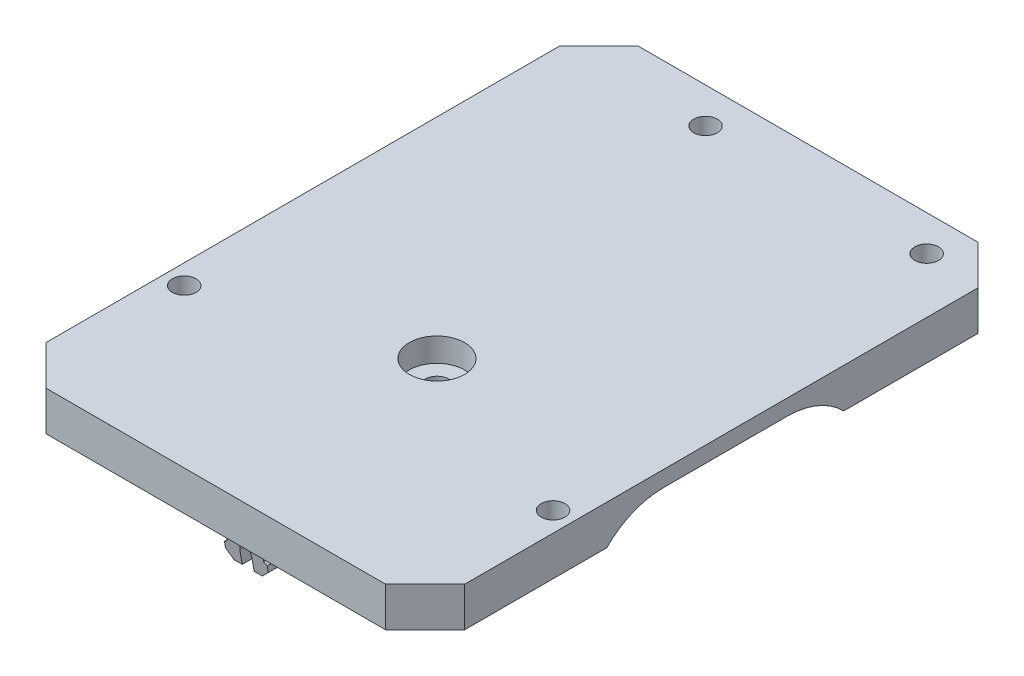
SolidWorks part; units mm, degrees
note: The reader was unsure of these and kept them because the rebuilt part matched: shared geometry of "Sketch2<3>".
ref_plane "Front Plane" through (0, 0, 0) normal (0, 0, 1) x (1, 0, 0)
ref_plane "Top Plane" through (0, 0, 0) normal (0, 1, 0) x (1, 0, 0)
ref_plane "Right Plane" through (0, 0, 0) normal (1, 0, 0) x (0, 0, -1)
sketch "Sketch1" plane through (0, 0, 0) normal (0, 1, 0) x (1, 0, 0)
  line L1 (-21.1416, 31.9378) -> (31.8584, 31.9378)
  line L2 (-21.1416, 31.9378) -> (-21.1416, -38.0622)
  line L3 (-21.1416, -38.0622) -> (31.8584, -38.0622)
  line L4 (31.8584, 31.9378) -> (31.8584, -38.0622)
  line L5 (31.8584, -38.0622) -> (-21.1416, -38.0622)
  line L6 (31.8584, -38.0622) -> (31.8584, -43.0622)
  line L7 (31.8584, -43.0622) -> (-21.1416, -43.0622)
  line L8 (-21.1416, -38.0622) -> (-21.1416, -43.0622)
  circle A0 centre (-18.6416, -23.0622) radius 1.5
  circle A1 centre (-3.1416, 27.4378) radius 1.5
  circle A2 centre (24.8584, 27.4378) radius 1.5
  circle A3 centre (29.3584, -24.3622) radius 1.5
  dimension "D8" = 3
  dimension "D9" = 2.5
  dimension "D10" = 13.7
  dimension "D1" = 53
  dimension "D2" = 70
  dimension "D3" = 28
  dimension "D4" = 7
  dimension "D5" = 65.5
  dimension "D6" = 15
  dimension "D7" = 50.5
  dimension "D11" = 5
extrude "Boss-Extrude1" add sketch "Sketch1" along normal blind 5 contours L3 L8 L7 L6 | L4 L1 L2 L3 A3 A2 A1 A0
sketch "Sketch2" plane through (0, 0, 0) normal (0, -1, 0) x (1, 0, 0)
  line L0 (8.3584, -9.9378) -> (8.3584, 5.0622)
  line L1 (8.3584, -9.9378) -> (2.3584, -9.9378)
  line L2 (2.3584, -9.9378) -> (2.3584, 5.0622)
  line L3 (8.3584, 5.0622) -> (2.3584, 5.0622)
  line L4 (8.3584, 25.0622) -> (8.3584, 40.0622)
  line L5 (8.3584, 25.0622) -> (2.3584, 25.0622)
  line L6 (2.3584, 25.0622) -> (2.3584, 40.0622)
  line L7 (8.3584, 40.0622) -> (2.3584, 40.0622)
  line L10 (-21.1416, -31.9378) -> (31.8584, -31.9378) construction
  line L11 (6.1084, -9.9378) -> (4.6084, -9.9378)
  line L12 (6.1084, -9.9378) -> (6.1084, 5.0622)
  line L13 (6.1084, 5.0622) -> (4.6084, 5.0622)
  line L14 (4.6084, -9.9378) -> (4.6084, 5.0622)
  line L15 (6.1084, 25.0622) -> (4.6084, 25.0622)
  line L16 (6.1084, 25.0622) -> (6.1084, 40.0622)
  line L17 (6.1084, 40.0622) -> (4.6084, 40.0622)
  line L18 (4.6084, 25.0622) -> (4.6084, 40.0622)
  line L19 (-21.1416, -31.9378) -> (-21.1416, 43.0622) construction
  circle A0 centre (5.3584, 15.0622) radius 1.5
  point P8 (5.3584, 25.0622)
  dimension "D4" = 3
  dimension "D8" = 10
  dimension "D1" = 15
  dimension "D2" = 6
  dimension "D3" = 20
  dimension "D5" = 3
  dimension "D6" = 23.5
  dimension "D7" = 22
  dimension "D9" = 1.5
  dimension "D10" = 2.25
extrude "Cut-Extrude1" cut sketch "Sketch2" against normal blind 10 contours A0
sketch "Sketch3" plane through (0, 5, 0) normal (0, 1, 0) x (1, 0, 0)
  circle A0 centre (5.3584, -15.0622) radius 3.5
  dimension "D1" = 7
extrude "Cut-Extrude2" cut sketch "Sketch3" against normal blind 3
extrude "Boss-Extrude2" add sketch "Sketch2<3>" along normal blind 6 contours L1 L14 L3 L2 | L12 L1 L0 L3 | L16 L5 L4 L7 | L5 L18 L7 L6
sketch "Sketch2<3>" plane through (0, 0, 0) normal (0, -1, 0) x (1, 0, 0) same geometry as "Sketch2"
sketch "Sketch4" plane through (0, 0, 40.0622) normal (0, 0, 1) x (1, 0, 0)
  line L0 (8.3584, -4.5) -> (8.3584, 0)
  line L1 (8.3584, 0) -> (7.6584, 0)
  line L3 (7.6584, 0) -> (7.6584, -4)
  line L4 (7.6584, -4) -> (8.0584, -4.2857)
  line L5 (8.3584, -6) -> (8.3584, 0) construction
  line L6 (2.6584, -4.2857) -> (3.0584, -4)
  line L7 (2.3584, -6) -> (2.3584, 0) construction
  line L8 (3.0584, -4) -> (3.0584, 0)
  line L10 (3.0584, 0) -> (2.3584, 0)
  line L11 (2.3584, 0) -> (2.3584, -4.5)
  line L12 (8.3584, -6) -> (6.1084, -6) construction
  line L13 (4.6084, -6) -> (2.3584, -6) construction
  line L14 (8.3584, -6) -> (7.1584, -6)
  line L15 (7.1584, -6) -> (8.0584, -5.1)
  line L16 (8.3584, -4.8) -> (8.3584, -6)
  line L17 (2.3584, -6) -> (2.3584, -4.8)
  line L18 (2.6584, -5.1) -> (3.5584, -6)
  line L19 (3.5584, -6) -> (2.3584, -6)
  line L20 (31.8584, 0) -> (-21.1416, 0) construction
  line L21 (4.6084, 0) -> (2.3584, 0) construction
  line L22 (8.0584, -5.1) -> (8.0584, -4.2857)
  line L23 (2.6584, -5.1) -> (2.6584, -4.2857)
  line L24 (8.3584, -6) -> (8.3584, 0) construction
  line L26 (2.3584, -6) -> (2.3584, 0) construction
  line L27 (2.3584, -4.8) -> (2.3584, -4.5)
  line L28 (8.3584, -4.8) -> (8.3584, -4.5)
  point P24 (3.4834, -6)
  dimension "D1" = 0.7
  dimension "D2" = 0.7
  dimension "D3" = 2
  dimension "D4" = 2
  dimension "D5" = 1.5
  dimension "D6" = 1.5
  dimension "D7" = 1.2
  dimension "D8" = 1.2
  dimension "D9" = 1.2
  dimension "D10" = 1.2
  dimension "D11" = 0.3
  dimension "D12" = 0.3
extrude "Cut-Extrude3" cut sketch "Sketch4" against normal through all
chamfer "Chamfer2" distance 0.75 angle 80 4 edges at (6.1084, 0, -2.4378) (4.6084, 0, -2.4378) (4.6084, 0, 32.5622) (6.1084, 0, 32.5622)
chamfer "Chamfer3" distance 1.1 angle 80 8 edges at (4.0834, -6, 40.0622) (6.6334, -6, 40.0622) (6.6334, -6, 5.0622) (4.0834, -6, 5.0622) (4.0834, -6, 25.0622) (6.6334, -6, 25.0622) (6.6334, -6, -9.9378) (4.0834, -6, -9.9378)
sketch "Sketch5" plane through (0, 0, 0) normal (0, -1, 0) x (1, 0, 0)
  line L0 (-21.1416, -31.9378) -> (-21.1416, 43.0622) construction
  line L1 (31.8584, -9.9378) -> (16.8584, -9.9378)
  line L2 (31.8584, -9.9378) -> (31.8584, 20.0622)
  line L3 (31.8584, 20.0622) -> (16.8584, 20.0622)
  line L4 (16.8584, -9.9378) -> (16.8584, 20.0622)
  line L6 (-21.1416, -9.9378) -> (-6.1416, -9.9378)
  line L7 (-21.1416, -9.9378) -> (-21.1416, 20.0622)
  line L8 (-21.1416, 20.0622) -> (-6.1416, 20.0622)
  line L9 (-6.1416, -9.9378) -> (-6.1416, 20.0622)
  line L10 (31.8584, -31.9378) -> (31.8584, 43.0622) construction
  point P4 (0, 0)
  point P10 (0, 0)
  dimension "D1" = 30
  dimension "D2" = 15
extrude "Cut-Extrude4" cut sketch "Sketch5" against normal blind 3
fillet "Fillet1" radius 10 6 edges at (24.3584, 3, -9.9378) (24.3584, 3, 20.0622) (-13.6416, 3, 20.0622) (-13.6416, 3, -9.9378) (-6.1416, 3, 5.0622) (16.8584, 3, 5.0622)
chamfer "Chamfer4" distance 5 angle 45 4 edges at (-21.1416, 2.5, -31.9378) (31.8584, 2.5, -31.9378) (31.8584, 2.5, 43.0622) (-21.1416, 2.5, 43.0622)
